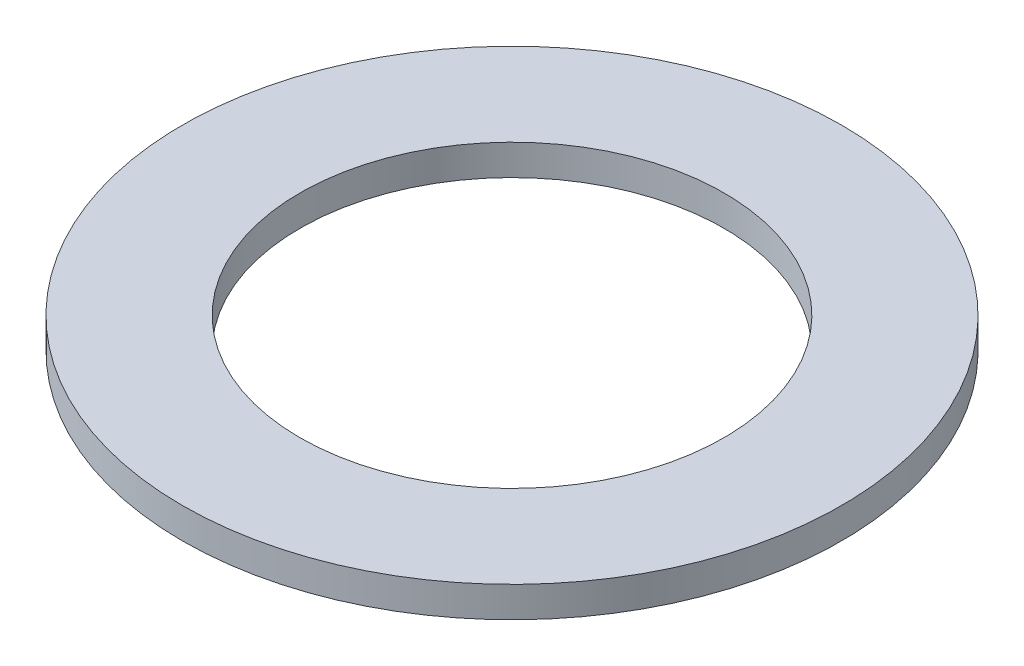
SolidWorks part; units mm, degrees
material "Beech"
ref_plane "Front Plane" through (0, 0, 0) normal (0, 0, 1) x (1, 0, 0)
ref_plane "Top Plane" through (0, 0, 0) normal (0, 1, 0) x (1, 0, 0)
ref_plane "Right Plane" through (0, 0, 0) normal (1, 0, 0) x (0, 0, -1)
sketch "Sketch1" plane through (0, 0, 0) normal (0, 1, 0) x (1, 0, 0)
  circle A0 centre (0, 0) radius 20.75
  circle A1 centre (0, 0) radius 32.25
  dimension "D1" = 41.5
  dimension "D2" = 64.5
extrude "Boss-Extrude1" add sketch "Sketch1" along normal blind 3
